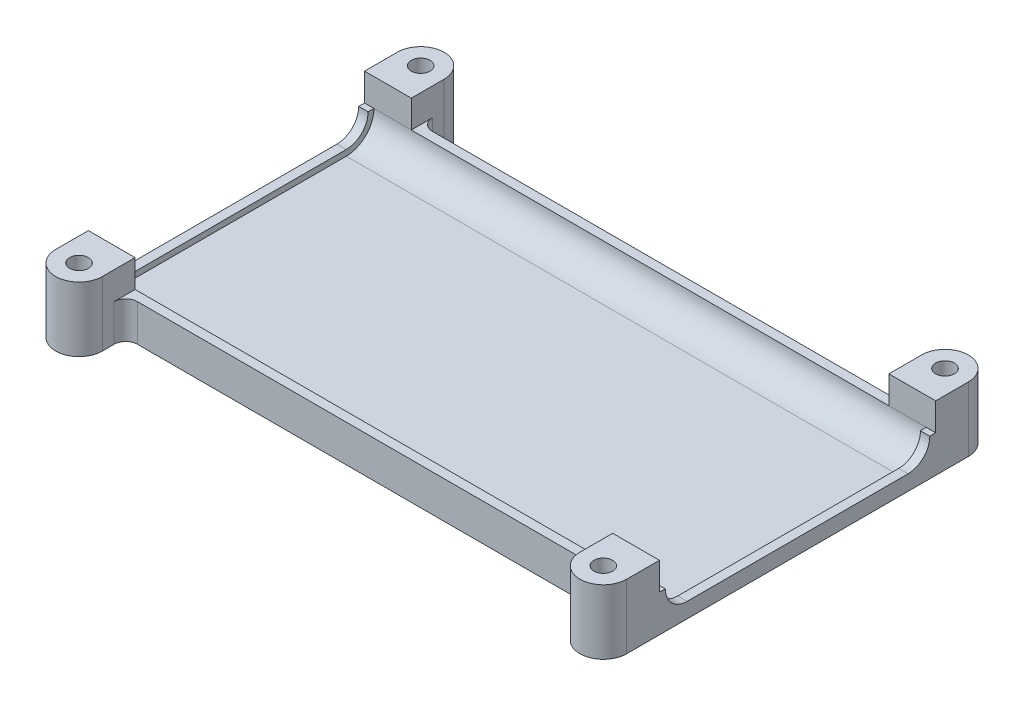
SolidWorks part; units mm, degrees
material "Nylon 101"
ref_plane "Front Plane" through (0, 0, 0) normal (0, 0, 1) x (1, 0, 0)
ref_plane "Top Plane" through (0, 0, 0) normal (0, 1, 0) x (1, 0, 0)
ref_plane "Right Plane" through (0, 0, 0) normal (1, 0, 0) x (0, 0, -1)
ref_axis "X AXIS" through (-88.99, 0, 0) along (1, 0, 0)
ref_axis "Y AXIS" through (0, -55, 0) along (0, 1, 0)
ref_axis "Z AXIS" through (0, 0, 55) along (0, 0, -1)
other "Freeze***"
sketch "Sketch1" plane through (0, 0, 0) normal (0, 1, 0) x (1, 0, 0)
  line L0 (77.54, -40.04) -> (77.54, 40.04)
  line L1 (-75, -37.5) -> (75, -37.5) construction
  line L2 (-75, -37.5) -> (-75, 37.5) construction
  line L3 (-75, 37.5) -> (75, 37.5) construction
  line L4 (75, -37.5) -> (75, 37.5) construction
  line L5 (0, 37.5) -> (0, -37.5) construction
  line L6 (-75, 0) -> (75, 0) construction
  line L7 (-64.84, 40.04) -> (64.84, 40.04)
  line L8 (-77.54, -40.04) -> (-77.54, 40.04)
  line L9 (-64.84, -40.04) -> (64.84, -40.04)
  line L10 (-77.54, 40.04) -> (-77.54, 46.39)
  line L11 (-64.84, 46.39) -> (-64.84, 40.04)
  line L12 (64.84, 46.39) -> (64.84, 40.04)
  line L13 (-77.54, 40.04) -> (77.54, 40.04) construction
  line L14 (77.54, 40.04) -> (77.54, 46.39)
  line L15 (77.54, -40.04) -> (77.54, -46.39)
  line L16 (64.84, -46.39) -> (64.84, -40.04)
  line L17 (-64.84, -46.39) -> (-64.84, -40.04)
  line L18 (-77.54, -40.04) -> (-77.54, -46.39)
  line L19 (-77.54, -40.04) -> (77.54, -40.04) construction
  arc A0 (-64.84, 46.39) -> (-77.54, 46.39) centre (-71.19, 46.39) ccw
  arc A1 (64.84, 46.39) -> (77.54, 46.39) centre (71.19, 46.39) cw
  arc A2 (64.84, -46.39) -> (77.54, -46.39) centre (71.19, -46.39) ccw
  arc A3 (-64.84, -46.39) -> (-77.54, -46.39) centre (-71.19, -46.39) cw
  point P0 (0, 0)
  point P13 (0, 0)
  point P14 (-68.3735, 42.9897)
  point P26 (68.015, 40.04)
  dimension "D4" = 12.7
  dimension "D1" = 150
  dimension "D2" = 75
  dimension "D3" = 2.54
extrude "Boss-Extrude1" add sketch "Sketch1" along normal blind 17.54
hole_wizard "#10 Clearance Hole1" positions "Sketch6" profile "Sketch7" hole size "#10" standard "ANSI Inch" end condition through all
sketch "Sketch6" plane through (0, 17.54, 0) normal (0, 1, 0) x (1, 0, 0)
  point P0 (-71.19, 46.39)
  point P3 (71.19, 46.39)
  point P6 (71.19, -46.39)
  point P9 (-71.19, -46.39)
sketch "Sketch7" plane through (-71.19, 17.54, -46.39) normal (1, 0, 0) x (0, 0, 1)
  line L0 (0, 0) -> (0, 17.54)
  line L1 (0, 17.54) -> (2.5527, 17.54)
  line L2 (2.5527, 17.54) -> (2.5527, 0)
  line L5 (2.5527, 0) -> (0, 0)
  line L11 (0, -6.35) -> (0, 107.95) construction
  dimension "Thru Hole Dia." = 5.1054
  dimension "Thru Hole Depth" = 17.54
sketch "Sketch3" plane through (0, 17.54, 0) normal (0, 1, 0) x (1, 0, 0)
  line L0 (-75, -37.5) -> (-75, 37.5) construction
  line L1 (-75, -37.5) -> (75, -37.5) construction
  line L2 (75, -37.5) -> (75, 37.5) construction
  line L3 (-75, 37.5) -> (75, 37.5) construction
  line L4 (-75, -37.5) -> (-75, 37.5)
  line L5 (-75, -37.5) -> (75, -37.5)
  line L6 (75, -37.5) -> (75, 37.5)
  line L7 (-75, 37.5) -> (75, 37.5)
extrude "Cut-Extrude1" cut sketch "Sketch3" against normal offset from surface (15 mm away) 2.54 up to face at (-71.19, 0, -43.8373)
sketch "Sketch4" plane through (0, 17.54, 0) normal (0, 1, 0) x (1, 0, 0)
  line L0 (-77.54, -40.04) -> (-77.54, 40.04) construction
  line L1 (-77.54, 35.9125) -> (77.54, 35.9125)
  line L2 (-77.54, 35.9125) -> (-77.54, -35.9125)
  line L3 (-77.54, -35.9125) -> (77.54, -35.9125)
  line L4 (77.54, 35.9125) -> (77.54, -35.9125)
  line L5 (77.54, -40.04) -> (77.54, 40.04) construction
  line L6 (-75, -37.5) -> (75, -37.5) construction
  point P8 (77.54, 0)
  dimension "D1" = 1.5875
extrude "Cut-Extrude2" cut sketch "Sketch4" against normal offset from surface (13.4125 mm away) 1.5875 up to face at (0, 2.54, 0)
sketch "Sketch8" plane through (0, 17.54, 0) normal (0, 1, 0) x (1, 0, 0)
  line L0 (-77.54, 46.39) -> (-77.54, 35.9125) construction
  line L1 (-77.54, 37.5) -> (-64.84, 37.5)
  line L2 (-77.54, 37.5) -> (-77.54, -37.5)
  line L3 (-77.54, -37.5) -> (-64.84, -37.5)
  line L4 (77.54, 37.5) -> (77.54, -37.5)
  line L5 (77.54, -46.39) -> (77.54, -35.9125) construction
  line L6 (-75, -37.5) -> (75, -37.5) construction
  line L7 (-75, 37.5) -> (75, 37.5) construction
  line L8 (-64.84, 40.04) -> (-64.84, 37.5)
  line L9 (-64.84, 40.04) -> (64.84, 40.04)
  line L10 (64.84, 40.04) -> (64.84, 37.5)
  line L11 (0, 0) -> (77.54, 0) construction
  line L12 (64.84, -40.04) -> (64.84, -37.5)
  line L13 (-64.84, -40.04) -> (64.84, -40.04)
  line L14 (-64.84, -40.04) -> (-64.84, -37.5)
  line L15 (64.84, 37.5) -> (77.54, 37.5)
  line L16 (64.84, -37.5) -> (77.54, -37.5)
extrude "Cut-Extrude3" cut sketch "Sketch8" against normal blind 7.5
fillet "Fillet2" radius 5.9125 4 edges at (-76.27, 4.1275, -35.9125) (-76.27, 4.1275, 35.9125) (76.27, 4.1275, 35.9125) (76.27, 4.1275, -35.9125)
fillet "Fillet1" radius 7.5 2 edges at (0, 2.54, 37.5) (0, 2.54, -37.5)
fillet "Fillet3" radius 3.175 4 edges at (64.84, 5.02, -40.04) (-64.84, 5.02, -40.04) (64.84, 5.02, 40.04) (-64.84, 5.02, 40.04)
